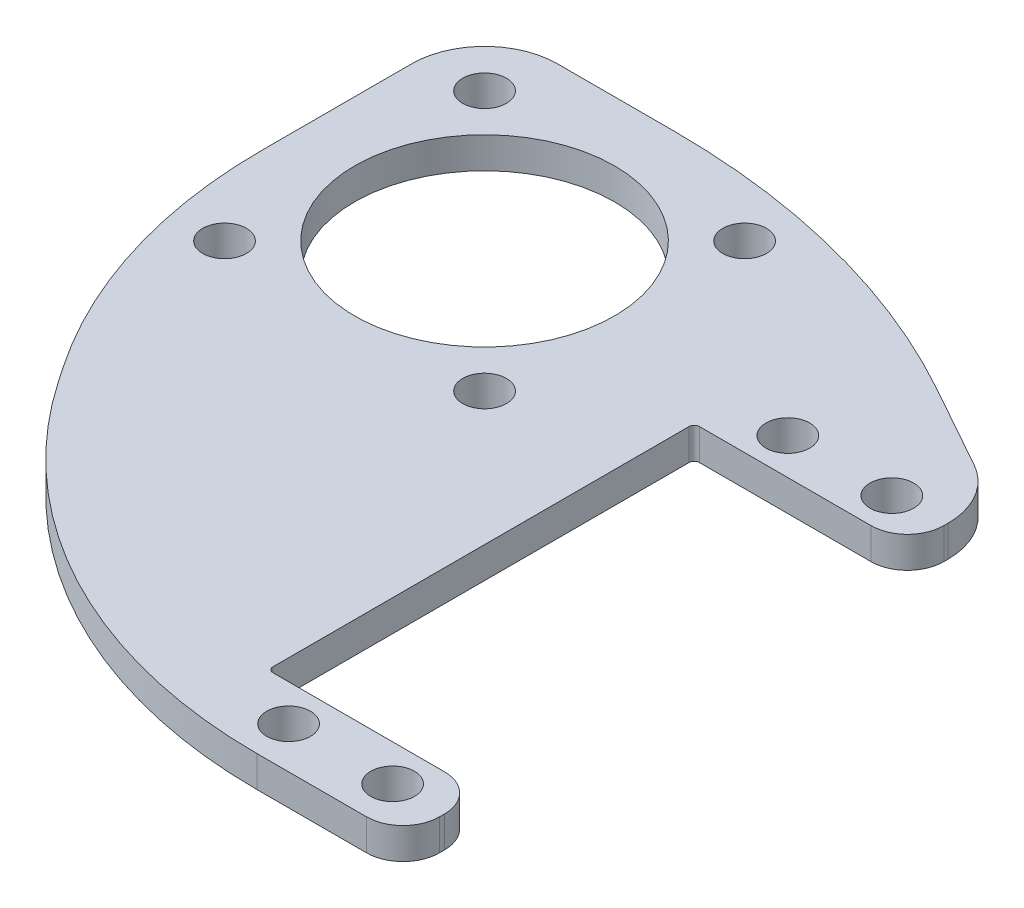
SolidWorks part; units mm, degrees
ref_plane "Płaszczyzna przednia" through (0, 0, 0) normal (0, 0, 1) x (1, 0, 0)
ref_plane "Płaszczyzna górna" through (0, 0, 0) normal (0, 1, 0) x (1, 0, 0)
ref_plane "Płaszczyzna prawa" through (0, 0, 0) normal (1, 0, 0) x (0, 0, -1)
ref_plane "Płaszczyzna1"
sketch "Szkic1" plane through (0, 0, 0) normal (0, 1, 0) x (-1, 0, 0)
  line L0 (18.25, 18.25) -> (-5.7881, 53.6295)
  line L1 (-5.7881, 53.6295) -> (-35.7881, 53.6295)
  line L2 (-35.7881, 53.6295) -> (-45.7881, 53.6295)
  line L3 (-45.7881, 53.6295) -> (-45.7881, 46.1295)
  line L4 (-45.7881, 46.1295) -> (-25.2881, 46.1295)
  line L5 (-25.2881, 46.1295) -> (-25.2881, 5.1295)
  line L6 (-25.2881, 5.1295) -> (-45.7881, 5.1295)
  line L7 (-45.7881, 5.1295) -> (-45.7881, -2.8705)
  line L8 (-45.7881, -2.8705) -> (-18.25, -18.25)
  line L9 (-18.25, -18.25) -> (18.25, -18.25)
  line L10 (18.25, -18.25) -> (18.25, 18.25)
  circle A0 centre (0, 0) radius 12.5
  circle A1 centre (-12.5, -12.5) radius 2.1
  circle A2 centre (12.5, -12.5) radius 2.1
  circle A3 centre (-30.7881, 1.6295) radius 2.1
  circle A4 centre (12.5, 12.5) radius 2.1
  circle A5 centre (-40.7881, 49.6295) radius 2.1
  circle A6 centre (-30.7881, 49.6295) radius 2.1
  circle A7 centre (-12.5, 12.5) radius 2.1
  circle A8 centre (-40.7881, 1.6295) radius 2.1
  dimension "D1" = 25
  dimension "D4" = 4.2
  dimension "D5" = 4.2
  dimension "D6" = 4.2
  dimension "D7" = 4.2
  dimension "D9" = 4.2
  dimension "D10" = 4.2
  dimension "D11" = 4.2
  dimension "D12" = 4.2
  dimension "D2" = 25
  dimension "D3" = 25
  dimension "D8" = 48
  dimension "D13" = 41
  dimension "D14" = 10
  dimension "D15" = 30
  dimension "D16" = 36.5
  dimension "D17" = 36.5
  dimension "D18" = 8
extrude "Wyciągnięcie proste1" add sketch "Szkic1" along normal blind 3 contours L9 L10 L0 L1 L2 L3 L4 L5 L6 L7 L8 A8 A7 A6 A5 A4 A3 A2 A1 A0 region at (11.1446, 0, 17.2173)
fillet "Zaokrąglenie1" radius 0.5 2 edges at (25.2881, 1.5, 46.1295) (25.2881, 1.5, 5.1295)
fillet "Zaokrąglenie3" radius 3.5 3 edges at (45.7881, 1.5, 53.6295) (45.7881, 1.5, 46.1295) (45.7881, 1.5, 5.1295)
fillet "Zaokrąglenie4" radius 7 1 edges at (45.7881, 1.5, -2.8705)
fillet "Zaokrąglenie5" radius 70 1 edges at (18.25, 1.5, -18.25)
fillet "Zaokrąglenie6" radius 49 1 edges at (5.7881, 1.5, 53.6295)
fillet "Zaokrąglenie7" radius 49 1 edges at (-18.25, 1.5, 18.25)
fillet "Zaokrąglenie8" radius 7 1 edges at (-18.25, 1.5, -18.25)
